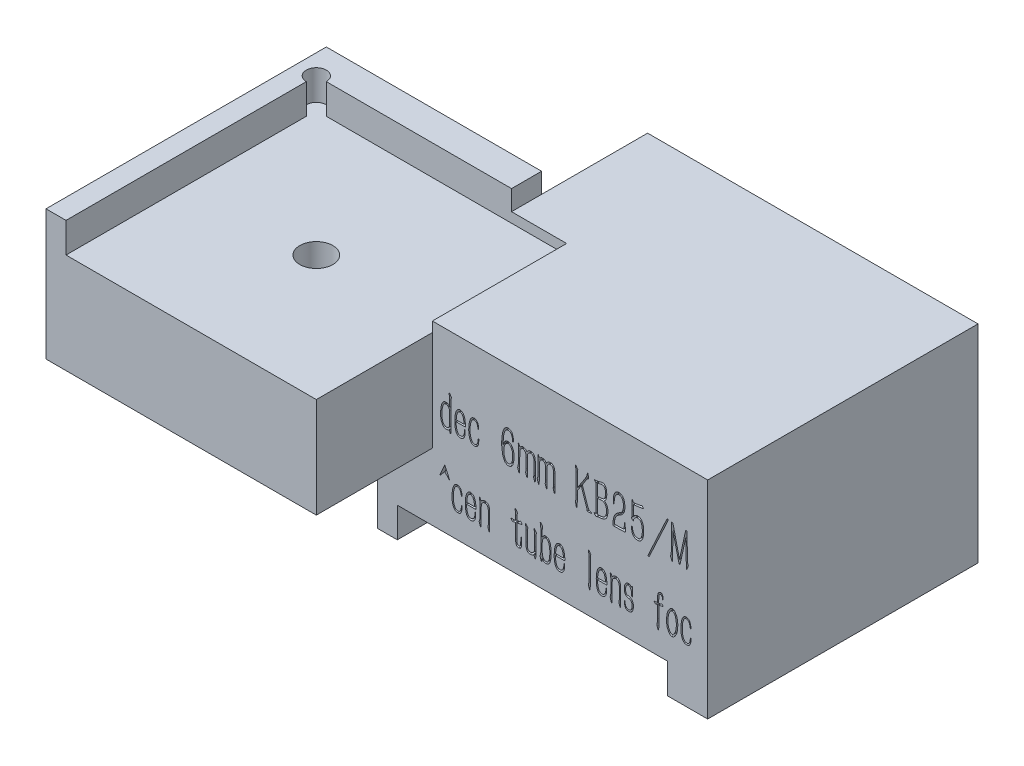
SolidWorks part; units mm, degrees
material "6061 合金"
ref_plane "前视基准面" through (0, 0, 0) normal (0, 0, 1) x (1, 0, 0)
ref_plane "上视基准面" through (0, 0, 0) normal (0, 1, 0) x (1, 0, 0)
ref_plane "右视基准面" through (0, 0, 0) normal (1, 0, 0) x (0, 0, -1)
sketch "草图1" plane through (0, 0, 0) normal (0, 1, 0) x (1, 0, 0)
  line L1 (-14.5, 14.5) -> (14.5, 14.5)
  line L2 (-14.5, 14.5) -> (-14.5, -14.5)
  line L3 (-14.5, -14.5) -> (14.5, -14.5)
  line L4 (14.5, 14.5) -> (14.5, -14.5)
  line L5 (-14.5, 14.5) -> (14.5, -14.5) construction
  line L6 (-14.5, -14.5) -> (14.5, 14.5) construction
  point P0 (0, 0)
  dimension "D1" = 29
  dimension "D2" = 29
extrude "凸台-拉伸1" add sketch "草图1" along normal blind 5
sketch "草图2" plane through (0, 5, 0) normal (0, -1, 0) x (1, 0, 0)
  line L1 (-12.5, 12.5) -> (12.5, 12.5)
  line L2 (-12.5, 12.5) -> (-12.5, -12.5)
  line L3 (-12.5, -12.5) -> (12.5, -12.5)
  line L4 (12.5, 12.5) -> (12.5, -12.5)
  line L5 (-12.5, 12.5) -> (12.5, -12.5) construction
  line L6 (-12.5, -12.5) -> (12.5, 12.5) construction
  point P0 (0, 0)
  dimension "D1" = 25
  dimension "D2" = 25
extrude "切除-拉伸1" cut sketch "草图2" along normal blind 3
sketch "草图3" plane through (0, 0, 0) normal (0, -1, 0) x (-1, 0, 0)
  line L1 (-14.5, -14.5) -> (20.5, -14.5)
  line L2 (-14.5, -14.5) -> (-14.5, 14.5)
  line L3 (-14.5, 14.5) -> (20.5, 14.5)
  line L4 (20.5, -14.5) -> (20.5, 14.5)
  dimension "D1" = 29
  dimension "D2" = 35
extrude "拉到底部滑块" add sketch "草图3" along normal up to surface (12.6823 mm away)
sketch "草图4" plane through (0, -12.6823, 0) normal (0, -1, 0) x (1, 0, 0)
  line L0 (0, 0) -> (-6, 0) construction
  line L1 (16.5, 0) -> (-16.5, 0) construction
  line L2 (-20.5, 14.5) -> (8.5, 14.5)
  line L3 (-18.5, 12.5) -> (6.5, 12.5)
  line L4 (-18.5, 12.5) -> (-18.5, -12.5)
  line L5 (-18.5, -12.5) -> (6.5, -12.5)
  line L6 (6.5, 12.5) -> (6.5, -12.5)
  line L7 (-18.5, 12.5) -> (6.5, -12.5) construction
  line L8 (-18.5, -12.5) -> (6.5, 12.5) construction
  line L9 (8.5, 14.5) -> (8.5, -14.5)
  line L10 (-20.5, -14.5) -> (8.5, -14.5)
  line L11 (-20.5, 14.5) -> (-20.5, -14.5)
  dimension "D1" = 6
  dimension "D2" = 25
  dimension "D3" = 25
  dimension "D4" = 2
extrude "凸台-拉伸3" add sketch "草图4" along normal blind 3
sketch "草图5" plane through (0, 2, 0) normal (0, 1, 0) x (1, 0, 0)
  circle A0 centre (0, 0) radius 2.1526
hole_wizard "M4 螺纹孔1" [suppressed] positions "3D草图1" profile "草图6" tap size "M4" standard "GB"
sketch3d "3D草图1"
  point P0 (0, 2, 0)
sketch "草图6" plane through (0, 2, 0) normal (1, 0, 0) x (0, 0, 1)
  line L0 (0, 0) -> (0, 11.0914)
  line L1 (0, 11.0914) -> (1.65, 10.1)
  line L2 (1.65, 10.1) -> (1.65, 0)
  line L5 (1.65, 0) -> (0, 0)
  line L10 (0, 11.0914) -> (-1.65, 10.1) construction
  line L11 (0, -6.35) -> (0, 107.95) construction
  dimension "螺纹孔钻头直径" = 3.3
  dimension "螺纹孔钻头深度" = 10.1
  dimension "导头角度" = 118
cosmetic thread "孔螺蚊线1" [suppressed] parameters "D1"=8, "D2"=4
sketch "草图7" plane through (0, -12.6823, 0) normal (0, -1, 0) x (1, 0, 0)
  line L0 (-6, 12.5) -> (-6, -12.5) construction
  line L1 (6.5, 12.5) -> (-18.5, 12.5) construction
  line L2 (-18.5, -12.5) -> (6.5, -12.5) construction
  circle A0 centre (-6, 0) radius 1.2473
hole_wizard "M4 螺纹孔2" positions "3D草图2" profile "草图8" tap size "M4" standard "GB"
sketch3d "3D草图2"
  point P0 (-6, -12.6823, 0)
sketch "草图8" plane through (-6, -12.6823, 0) normal (1, 0, 0) x (0, 0, -1)
  line L0 (0, 0) -> (0, 11.0914)
  line L1 (0, 11.0914) -> (1.65, 10.1)
  line L2 (1.65, 10.1) -> (1.65, 0)
  line L5 (1.65, 0) -> (0, 0)
  line L10 (0, 11.0914) -> (-1.65, 10.1) construction
  line L11 (0, -6.35) -> (0, 107.95) construction
  dimension "螺纹孔钻头直径" = 3.3
  dimension "螺纹孔钻头深度" = 10.1
  dimension "导头角度" = 118
cosmetic thread "孔螺蚊线2" parameters "D1"=8, "D2"=4
sketch "草图9" plane through (0, 5, 0) normal (0, 1, 0) x (1, 0, 0)
  circle A0 centre (-12.5, 12.5) radius 1
extrude "切除-拉伸2" cut sketch "草图9" against normal up to surface (3 mm away) up to face at (0, 2, 0)
sketch "草图10" plane through (0, -15.6823, 0) normal (0, -1, 0) x (1, 0, 0)
  circle A0 centre (-18.5, -12.5) radius 1
extrude "切除-拉伸3" cut sketch "草图10" against normal up to surface (3 mm away) up to face at (-6, -12.6823, -1.65)
sketch "草图11" plane through (-14.5, 0, 0) normal (-1, 0, 0) x (0, 0, 1)
  line L4 (-14.5, 0) -> (14.5, 0)
  line L5 (14.5, 0) -> (14.5, 5)
  line L6 (14.5, 5) -> (-14.5, 5)
  line L7 (-14.5, 5) -> (-14.5, 0)
  line L8 (-14.5, 0) -> (14.5, 0)
  line L9 (14.5, 0) -> (14.5, 5)
  line L10 (14.5, 5) -> (-14.5, 5)
  line L11 (-14.5, 5) -> (-14.5, 0)
  dimension "D1" = 0
extrude "凸台-拉伸4" add sketch "草图11" along normal up to surface (6 mm away) up to face at (-20.5, -7.8412, 0)
sketch "草图12" plane through (8.5, 0, 0) normal (1, 0, 0) x (0, 0, -1)
  line L4 (14.5, -12.6823) -> (-14.5, -12.6823)
  line L5 (-14.5, -12.6823) -> (-14.5, -15.6823)
  line L6 (-14.5, -15.6823) -> (14.5, -15.6823)
  line L7 (14.5, -15.6823) -> (14.5, -12.6823)
  line L8 (14.5, -12.6823) -> (-14.5, -12.6823)
  line L9 (-14.5, -12.6823) -> (-14.5, -15.6823)
  line L10 (-14.5, -15.6823) -> (14.5, -15.6823)
  line L11 (14.5, -15.6823) -> (14.5, -12.6823)
  dimension "D1" = 0
extrude "凸台-拉伸5" add sketch "草图12" along normal up to surface (6 mm away) up to face at (14.5, -3.8412, 0)
sketch "草图13" plane through (6.5, 0, 0) normal (-1, 0, 0) x (0, 0, 1)
  line L4 (12.5, -12.6823) -> (-12.5, -12.6823)
  line L5 (-12.5, -12.6823) -> (-12.5, -15.6823)
  line L6 (-12.5, -15.6823) -> (12.5, -15.6823)
  line L7 (12.5, -15.6823) -> (12.5, -12.6823)
  line L8 (12.5, -12.6823) -> (-12.5, -12.6823)
  line L9 (-12.5, -12.6823) -> (-12.5, -15.6823)
  line L10 (-12.5, -15.6823) -> (12.5, -15.6823)
  line L11 (12.5, -15.6823) -> (12.5, -12.6823)
  dimension "D1" = 0
extrude "切除-拉伸4" cut sketch "草图13" against normal blind 2
sketch "草图14" plane through (0, 0, 12.5) normal (0, 0, -1) x (-1, 0, 0)
  line L4 (18.5, -12.6823) -> (-8.5, -12.6823)
  line L5 (-8.5, -12.6823) -> (-8.5, -15.6823)
  line L6 (-8.5, -15.6823) -> (18.5, -15.6823)
  line L7 (18.5, -15.6823) -> (18.5, -12.6823)
  line L8 (18.5, -12.6823) -> (-8.5, -12.6823)
  line L9 (-8.5, -12.6823) -> (-8.5, -15.6823)
  line L10 (-8.5, -15.6823) -> (18.5, -15.6823)
  line L11 (18.5, -15.6823) -> (18.5, -12.6823)
  dimension "D1" = 0
extrude "切除-拉伸5" cut sketch "草图14" against normal through all
fillet "圆角1" radius 1 1 edges at (8.5, -14.1823, -12.5)
sketch "草图15" plane through (12.5, 0, 0) normal (-1, 0, 0) x (0, 0, 1)
  line L4 (12.5, 5) -> (-12.5, 5)
  line L5 (-12.5, 5) -> (-12.5, 2)
  line L6 (-12.5, 2) -> (12.5, 2)
  line L7 (12.5, 2) -> (12.5, 5)
  line L8 (12.5, 5) -> (-12.5, 5)
  line L9 (-12.5, 5) -> (-12.5, 2)
  line L10 (-12.5, 2) -> (12.5, 2)
  line L11 (12.5, 2) -> (12.5, 5)
  dimension "D1" = 0
sketch "草图16" plane through (0, 0, 12.5) normal (0, 0, -1) x (-1, 0, 0)
  line L4 (12.5, 5) -> (-14.5, 5)
  line L5 (-14.5, 5) -> (-14.5, 2)
  line L6 (-14.5, 2) -> (12.5, 2)
  line L7 (12.5, 2) -> (12.5, 5)
  line L8 (12.5, 5) -> (-14.5, 5)
  line L9 (-14.5, 5) -> (-14.5, 2)
  line L10 (-14.5, 2) -> (12.5, 2)
  line L11 (12.5, 2) -> (12.5, 5)
  dimension "D1" = 0
sketch "草图17" plane through (0, 5, 0) normal (0, 1, 0) x (1, 0, 0)
  line L0 (-20.5, -14.5) -> (14.5, -14.5) construction
  line L1 (14.5, -14.5) -> (14.5, 14.5) construction
  line L2 (-20.5, -14.5) -> (14.5, -14.5)
  line L3 (14.5, -14.5) -> (14.5, 14.5)
  line L4 (-20.5, -12.5) -> (12.5, -12.5)
  line L5 (12.5, -12.5) -> (12.5, 14.5)
  line L6 (12.5, 14.5) -> (14.5, 14.5)
  line L7 (-20.5, -12.5) -> (-20.5, -14.5)
  dimension "D1" = 2
extrude "切除-拉伸8" cut sketch "草图17" against normal through all
sketch "草图19" plane through (0, 0, 12.5) normal (0, 0, 1) x (1, 0, 0)
  text T0 "dec 6mm KB25/M \r\n^cen tube lens foc"
extrude "切除-拉伸9" cut sketch "草图19" against normal blind 0.5
sketch "草图20" plane through (0, 2, 0) normal (0, 1, 0) x (1, 0, 0)
  line L4 (12.5, 12.5) -> (-11.5, 12.5)
  line L5 (-12.5, 11.5) -> (-12.5, -12.5)
  line L6 (-12.5, -12.5) -> (12.5, -12.5)
  line L7 (12.5, -12.5) -> (12.5, 12.5)
  line L8 (12.5, 12.5) -> (-11.5, 12.5)
  line L9 (-12.5, 11.5) -> (-12.5, -12.5)
  line L10 (-12.5, -12.5) -> (12.5, -12.5)
  line L11 (12.5, -12.5) -> (12.5, 12.5)
  arc A1 (-11.5, 12.5) -> (-12.5, 11.5) centre (-12.5, 12.5) ccw
  arc A2 (-11.5, 12.5) -> (-12.5, 11.5) centre (-12.5, 12.5) ccw
  dimension "D1" = 0
extrude "凸台-拉伸6" add sketch "草图20" along normal up to surface (3 mm away) up to face at (-7.6724, 5, -5.9582)
sketch "草图23" plane through (0, 5, 0) normal (0, 1, 0) x (1, 0, 0)
  line L1 (-15, 0.91) -> (-40, 0.91)
  line L2 (-15, 0.91) -> (-15, -24.09)
  line L3 (-15, -24.09) -> (-40, -24.09)
  line L4 (-40, 0.91) -> (-40, -24.09)
  line L5 (-15, 0.91) -> (-40, -24.09) construction
  line L6 (-15, -24.09) -> (-40, 0.91) construction
  circle A0 centre (-27.5, -11.59) radius 2.1177
  circle A2 centre (-6, 0) radius 1.2473 construction
  point P0 (-27.5, -11.59)
  dimension "D4" = 21.5
  dimension "D1" = 25
  dimension "D2" = 25
  dimension "D3" = 11.59
sketch "草图21" plane through (0, 5, 0) normal (0, 1, 0) x (1, 0, 0)
  line L1 (-15, 3.91) -> (-42, 3.91)
  line L2 (-15, 3.91) -> (-15, -24.09)
  line L3 (-15, -24.09) -> (-42, -24.09)
  line L4 (-42, 3.91) -> (-42, -24.09)
  line L6 (-40, 0.91) -> (-40, -24.09) construction
  line L7 (-15, 0.91) -> (-15, -24.09) construction
  line L8 (-15, -24.09) -> (-40, -24.09) construction
  line L9 (-15, 0.91) -> (-40, 0.91) construction
  dimension "D1" = 2
  dimension "D2" = 3
extrude "凸台-拉伸7" add sketch "草图21" along normal blind 2 and the other way blind 11
sketch "草图25" plane through (0, 7, 0) normal (0, 1, 0) x (1, 0, 0)
  line L0 (-40, 0.91) -> (-40, -24.09) construction
  line L1 (-15, -24.09) -> (-40, -24.09) construction
  line L2 (-15, 0.91) -> (-15, -24.09) construction
  line L3 (-15, 0.91) -> (-40, 0.91) construction
  line L4 (-40, 0.91) -> (-40, -24.09)
  line L5 (-15, -24.09) -> (-40, -24.09)
  line L6 (-15, 0.91) -> (-15, -24.09)
  line L7 (-15, 0.91) -> (-40, 0.91)
extrude "切除-拉伸10" cut sketch "草图25" against normal blind 3
sketch "草图26" plane through (0, 7, 0) normal (0, 1, 0) x (1, 0, 0)
  circle A0 centre (-40, 0.91) radius 1
extrude "切除-拉伸11" cut sketch "草图26" against normal up to surface (3 mm away) up to face at (-25, 4, 11.772)
sketch "草图27" plane through (0, 5, 0) normal (0, 1, 0) x (1, 0, 0)
  line L1 (-20.5, 3.91) -> (-15, 3.91)
  line L2 (-20.5, 3.91) -> (-20.5, 0.91)
  line L3 (-20.5, 0.91) -> (-15, 0.91)
  line L4 (-15, 3.91) -> (-15, 0.91)
extrude "切除-拉伸17" cut sketch "草图27" along normal through all
hole_wizard "M4 螺纹孔3" positions "3D草图3" profile "草图28" tap size "M4" standard "GB" end condition through all
sketch3d "3D草图3"
  point P0 (-27.5, 5, 11.59)
sketch "草图28" plane through (-27.5, 5, 11.59) normal (1, 0, 0) x (0, 0, 1)
  line L0 (0, 0) -> (0, 20.6823)
  line L1 (0, 20.6823) -> (1.65, 20.6823)
  line L2 (1.65, 20.6823) -> (1.65, 0)
  line L5 (1.65, 0) -> (0, 0)
  line L11 (0, -6.35) -> (0, 107.95) construction
  dimension "通孔螺纹孔钻头直径" = 3.3
  dimension "通孔螺纹孔钻头深度" = 20.6823
cosmetic thread "孔螺蚊线3" parameters "D2"=4
